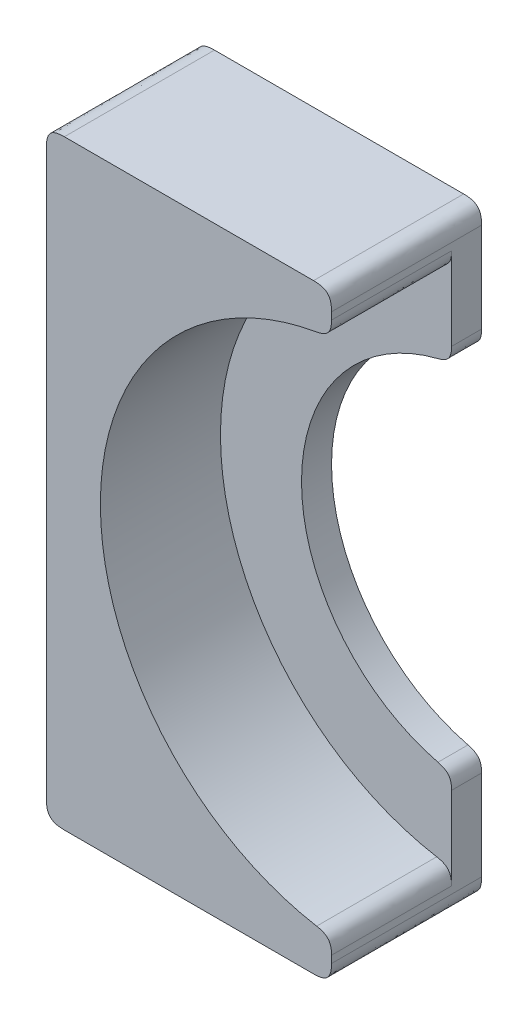
SolidWorks part; units mm, degrees
ref_plane "Front Plane" through (0, 0, 0) normal (0, 0, 1) x (1, 0, 0)
ref_plane "Top Plane" through (0, 0, 0) normal (0, 1, 0) x (1, 0, 0)
ref_plane "Right Plane" through (0, 0, 0) normal (1, 0, 0) x (0, 0, -1)
sketch "Sketch1" plane through (0, 0, 0) normal (0, 0, 1) x (1, 0, 0)
  line L0 (0, 50) -> (0, -50) construction
  line L1 (-52.5, 50) -> (52.5, 50)
  line L2 (-52.5, 50) -> (-52.5, -50)
  line L3 (-52.5, -50) -> (52.5, -50)
  line L4 (52.5, 50) -> (52.5, -50)
  line L5 (-52.5, 50) -> (52.5, -50) construction
  line L6 (-52.5, -50) -> (52.5, 50) construction
  line L7 (-5, -50) -> (-5, 50)
  line L8 (5, 50) -> (5, -50)
  line L9 (-5, 46.4347) -> (5, 46.4347) construction
  circle A0 centre (0, 0) radius 43.5
  circle A1 centre (0, 0) radius 30
  point P0 (0, 0)
  point P16 (0, 46.4347)
  dimension "D2" = 87
  dimension "D3" = 10
  dimension "D4" = 100
  dimension "D5" = 60
  dimension "D1" = 105
extrude "Boss-Extrude1" add sketch "Sketch1" along normal blind 25 contours A0 L7 L1 L2 L3 region at (-28.75, 48.8929, 0)
extrude "Boss-Extrude2" add sketch "Sketch1<3>" along normal blind 5 contours L7 A0 region at (-5.9461, 36.396, 0)
sketch "Sketch1<3>" plane through (0, 0, 0) normal (0, 0, 1) x (1, 0, 0) same geometry as "Sketch1"
fillet "Fillet1" radius 3 8 edges at (-52.5, -50, 12.5) (-52.5, 50, 12.5) (-5, 50, 12.5) (-5, 43.2117, 15) (-5, 29.5804, 2.5) (-5, -29.5804, 2.5) (-5, -43.2117, 15) (-5, -50, 12.5) conic rho 0.55
